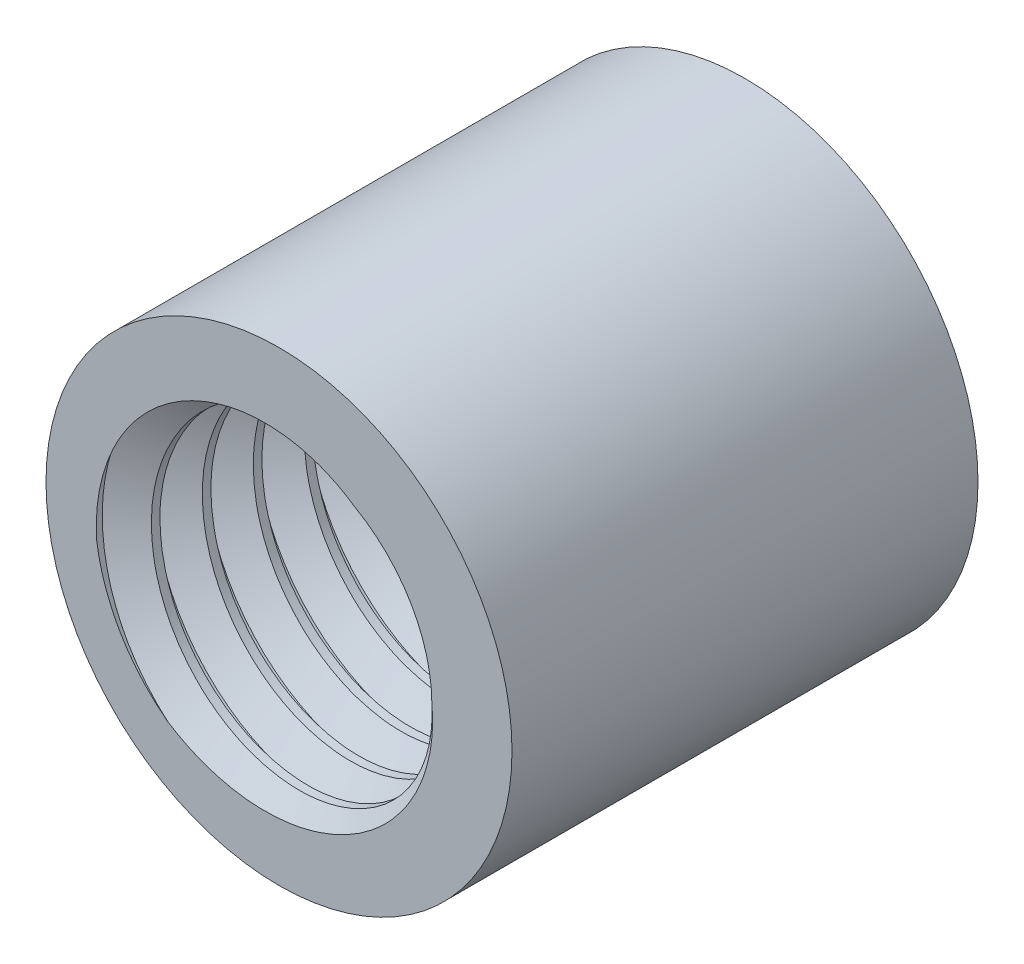
SolidWorks part; units mm, degrees
ref_plane "Plan de face" through (0, 0, 0) normal (0, 0, 1) x (1, 0, 0)
ref_plane "Plan de dessus" through (0, 0, 0) normal (0, 1, 0) x (1, 0, 0)
ref_plane "Plan de droite" through (0, 0, 0) normal (1, 0, 0) x (0, 0, -1)
sketch "Esquisse1" plane through (0, 0, 0) normal (0, 0, 1) x (1, 0, 0)
  circle A0 centre (0, 0) radius 5.25
  circle A1 centre (0, 0) radius 8
  dimension "D1" = 16
  dimension "D2" = 10.5
extrude "Boss.-Extru.1" add sketch "Esquisse1" along normal blind 16
sketch "Esquisse2" plane through (0, 0, 16) normal (0, 0, 1) x (1, 0, 0)
  circle A0 centre (0, 0) radius 5.25 construction
  circle A1 centre (0, 0) radius 5.25
curve "Hélice/Spirale1" pitch 1.75 height 35 radius 5.25 centre (0, 0, 16) axis (0, 0, -1) start towards (1, 0, 0)
sketch "Esquisse3" plane through (0, 0, 0) normal (0, 1, 0) x (1, 0, 0)
  line L0 (5.25, -16) -> (5.25, -17.4555)
  line L1 (5.25, -17.4555) -> (6.32, -16.8378)
  line L2 (6.32, -16.8378) -> (6.32, -16.6178)
  line L3 (6.32, -16.6178) -> (5.25, -16)
  line L4 (5.0182, -16.7278) -> (8.4632, -16.7278) construction
  dimension "D1" = 0.11
  dimension "D2" = 0.11
  dimension "D3" = 60
  dimension "D4" = 60
  dimension "D5" = 1.07
sweep "Enlèvement de matière-Balayage1" cut profiles "Esquisse3" path "Hélice/Spirale1"
